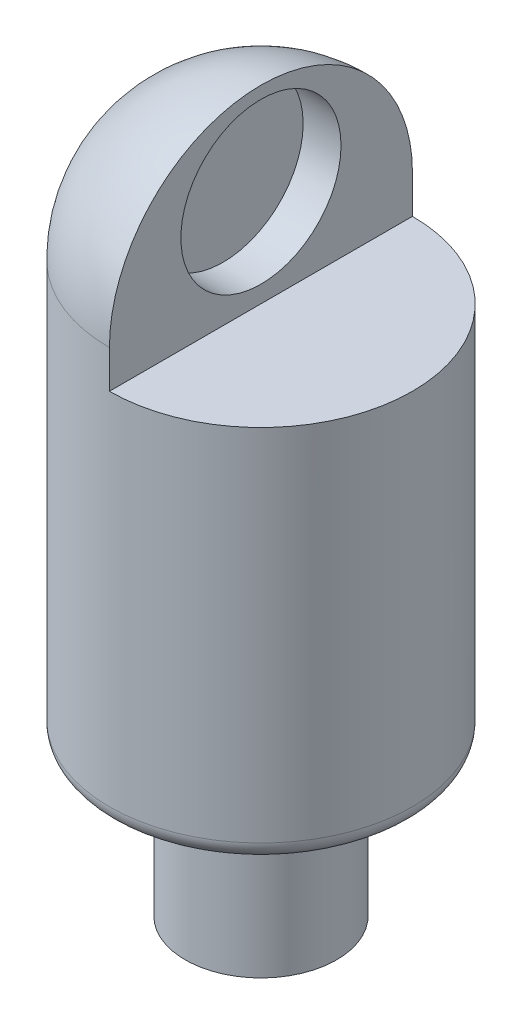
SolidWorks part; units mm, degrees
ref_plane "Front Plane" through (0, 0, 0) normal (0, 0, 1) x (1, 0, 0)
ref_plane "Top Plane" through (0, 0, 0) normal (0, 1, 0) x (1, 0, 0)
ref_plane "Right Plane" through (0, 0, 0) normal (1, 0, 0) x (0, 0, -1)
sketch "Sketch1" plane through (0, 0, 0) normal (0, 1, 0) x (1, 0, 0)
  circle A0 centre (0, 0) radius 40
extrude "Boss-Extrude1" add sketch "Sketch1" along normal blind 150
sketch "Sketch2" plane through (0, 0, 0) normal (0, -1, 0) x (1, 0, 0)
  circle A0 centre (0, 0) radius 20
extrude "Boss-Extrude2" add sketch "Sketch2" along normal blind 40
sketch "Sketch3" plane through (0, 150, 0) normal (0, 1, 0) x (1, 0, 0)
  line L0 (0, 40) -> (0, -40)
  line L1 (0, 40) -> (40.5161, 40)
  line L2 (0, -40) -> (40.5161, -40)
  line L3 (40.5161, 40) -> (40.5161, -40)
  circle A0 centre (0, 0) radius 40 construction
extrude "Cut-Extrude1" cut sketch "Sketch3" against normal blind 50
sketch "Sketch4" plane through (0, 0, 0) normal (1, 0, 0) x (0, 0, -1)
  circle A0 centre (0, 125.623) radius 21.1418
extrude "Cut-Extrude2" cut sketch "Sketch4" against normal blind 10
fillet "Fillet1" radius 40 1 edges at (-40, 150, 0)
fillet "Fillet2" radius 5 1 edges at (0, 0, 40)
equation "\"0..4m\"=0.15"
